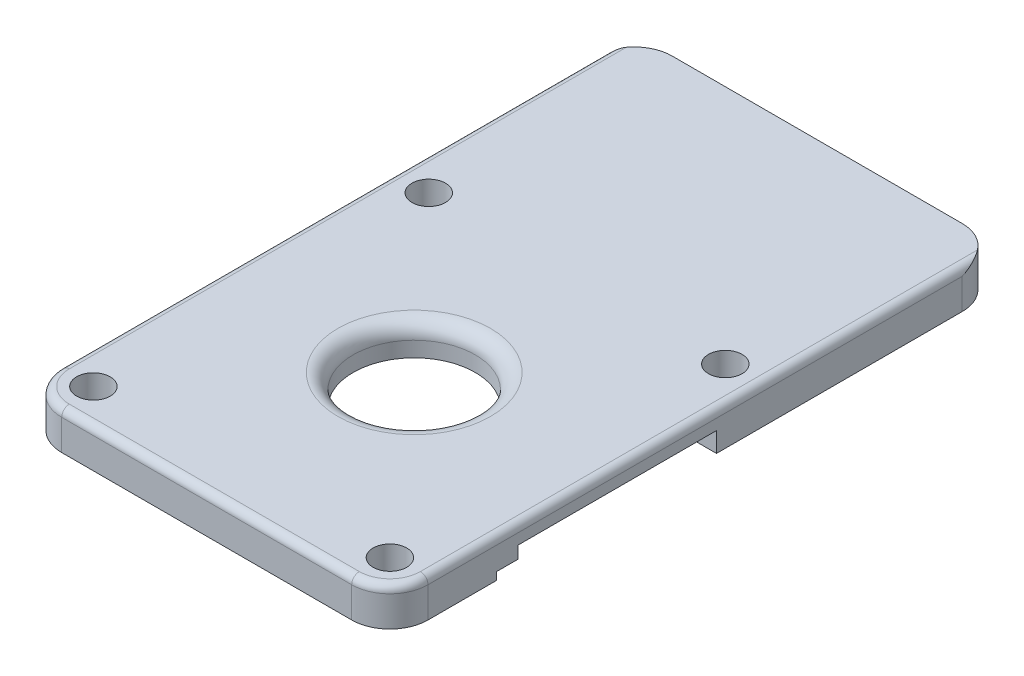
SolidWorks part; units mm, degrees
ref_plane "前视基准面" through (0, 0, 0) normal (0, 0, 1) x (1, 0, 0)
ref_plane "上视基准面" through (0, 0, 0) normal (0, 1, 0) x (1, 0, 0)
ref_plane "右视基准面" through (0, 0, 0) normal (1, 0, 0) x (0, 0, -1)
sketch "草图1" plane through (0, 0, 0) normal (0, 1, 0) x (1, 0, 0)
  line L0 (-12, 10.776) -> (-12, 24.224)
  line L18 (-9.5, 13.276) -> (9.5, 13.276) construction
  line L19 (-12, 10.776) -> (-12, -10.776)
  line L20 (-9.5, -13.276) -> (9.5, -13.276)
  line L21 (12, 10.776) -> (12, -10.776)
  line L22 (-12, 13.276) -> (12, -13.276) construction
  line L23 (-12, -13.276) -> (12, 13.276) construction
  line L24 (-9.5, 26.724) -> (9.5, 26.724)
  line L25 (12, 24.224) -> (12, 10.776)
  line L26 (-19.3805, 0) -> (19.2101, 0) construction
  line L27 (0, 33.0534) -> (0, -22.2948) construction
  line L37 (-9.715, 10.985) -> (9.715, -10.985) construction
  line L38 (-9.715, -10.985) -> (9.715, 10.985) construction
  line L39 (-9.714, 10.986) -> (9.714, 10.986) construction
  line L40 (-9.714, 10.986) -> (-9.714, -10.986) construction
  line L41 (-9.714, -10.986) -> (9.714, -10.986) construction
  line L42 (9.714, 10.986) -> (9.714, -10.986) construction
  line L43 (-9.714, 10.986) -> (9.714, -10.986) construction
  line L44 (-9.714, -10.986) -> (9.714, 10.986) construction
  arc A4 (-9.5, 13.276) -> (-12, 10.776) centre (-9.5, 10.776) ccw construction
  arc A5 (-9.5, -13.276) -> (-12, -10.776) centre (-9.5, -10.776) cw
  arc A6 (9.5, -13.276) -> (12, -10.776) centre (9.5, -10.776) ccw
  arc A7 (12, 10.776) -> (9.5, 13.276) centre (9.5, 10.776) ccw construction
  arc A8 (12, 24.224) -> (9.5, 26.724) centre (9.5, 24.224) ccw
  arc A9 (-12, 24.224) -> (-9.5, 26.724) centre (-9.5, 24.224) cw
  circle A12 centre (-9.714, -10.986) radius 2.2002
  circle A13 centre (-9.714, -10.986) radius 1.1
  circle A14 centre (9.714, -10.986) radius 1.1
  circle A15 centre (9.714, -10.986) radius 2.2002
  circle A16 centre (9.714, 10.986) radius 2.2002
  circle A17 centre (9.714, 10.986) radius 1.1
  circle A18 centre (-9.714, 10.986) radius 1.1
  circle A19 centre (-9.714, 10.986) radius 2.2002
  circle A20 centre (0, 0.32) radius 4
  point P0 (0, 0)
  point P28 (0, 0)
  point P34 (0, 0)
  dimension "D5" = 40
  dimension "D6" = 2.5
  dimension "D7" = 19.428
  dimension "D8" = 21.972
  dimension "D3" = 2.5
  dimension "D4" = 2.5
  dimension "D9" = 13.596
  dimension "D1" = 24
  dimension "D2" = 26.552
extrude "凸台-拉伸1" add sketch "草图1" against normal blind 2.5 contours A6 A15 L21 L25 A8 L24 A9 L0 L19 A5 A12 L20 A20 A16 A19 | A16 A17 | A19 A18 | A12 A13 | A15 A14
sketch "草图2" plane through (12, 0, 0) normal (1, 0, 0) x (0, 0, -1)
  line L0 (24.224, -2.5) -> (-10.776, -2.5) construction
  line L1 (-6.276, -2.5) -> (8.124, -2.5)
  line L2 (-6.276, -2.5) -> (-6.276, -2)
  line L3 (-6.276, -2) -> (8.124, -2)
  line L4 (8.124, -2.5) -> (8.124, -2)
  line L5 (-13.276, -2.5) -> (-13.276, 0) construction
  point P8 (8.124, -2.25)
  dimension "D1" = 21.4
  dimension "D2" = 7
  dimension "D3" = 0.5
extrude "切除-拉伸1" cut sketch "草图2" against normal through all
sketch "草图3" plane through (12, 0, 0) normal (1, 0, 0) x (0, 0, -1)
  line L0 (-13.276, -2.5) -> (-13.276, 0) construction
  line L1 (8.124, -2.5) -> (-4.876, -2.5)
  line L2 (8.124, -2.5) -> (8.124, -1.2)
  line L3 (8.124, -1.2) -> (-4.876, -1.2)
  line L4 (-4.876, -2.5) -> (-4.876, -1.2)
  dimension "D1" = 1.3
  dimension "D2" = 8.4
  dimension "D3" = 21.4
extrude "切除-拉伸2" cut sketch "草图3" against normal blind 4.5
sketch "草图4" plane through (-12, 0, 0) normal (-1, 0, 0) x (0, 0, 1)
  line L4 (-8.124, -2.5) -> (4.876, -2.5)
  line L5 (4.876, -2.5) -> (4.876, -1.2)
  line L6 (4.876, -1.2) -> (-8.124, -1.2)
  line L7 (-8.124, -1.2) -> (-8.124, -2.5)
  line L24 (-8.124, -2.5) -> (4.876, -2.5)
  line L25 (4.876, -2.5) -> (4.876, -1.2)
  line L26 (4.876, -1.2) -> (-8.124, -1.2)
  line L27 (-8.124, -1.2) -> (-8.124, -2.5)
  dimension "D2" = 0
extrude "切除-拉伸3" cut sketch "草图4" against normal blind 4.5 contours L24 L25 L26 L27
sketch "草图5" plane through (0, -2.5, 0) normal (0, -1, 0) x (1, 0, 0)
  line L0 (-12, -8.124) -> (12, -8.124) construction
  line L1 (-4, -8.124) -> (7.5, -8.124)
  line L2 (-4, -8.124) -> (-4, -25.424)
  line L3 (-4, -25.424) -> (7.5, -25.424)
  line L4 (7.5, -8.124) -> (7.5, -25.424)
  line L6 (7.5, -8.124) -> (7.5, 4.876) construction
  line L7 (12, -24.224) -> (12, -8.124) construction
  line L8 (-9.5, -26.724) -> (9.5, -26.724) construction
  dimension "D1" = 16
  dimension "D2" = 1.3
extrude "切除-拉伸11" cut sketch "草图5" against normal up to surface (0.5 mm away) contours L2 L1 L4 L3 up to face at (0, -2, 1.976)
sketch "草图6" plane through (0, -2, 0) normal (0, -1, 0) x (1, 0, 0)
  line L0 (-4, -8.124) -> (-4, -25.424) construction
  line L5 (-4, -8.124) -> (2, -8.124)
  line L6 (-4, -8.124) -> (-4, -18.124)
  line L7 (-4, -18.124) -> (2, -18.124)
  line L8 (2, -8.124) -> (2, -18.124)
  line L9 (-7.5, -8.124) -> (-4, -8.124) construction
  line L10 (12, -24.224) -> (12, -8.124) construction
  line L11 (-12, -8.124) -> (-4, -8.124) construction
  dimension "D1" = 10
  dimension "D2" = 10
extrude "切除-拉伸12" cut sketch "草图6" against normal blind 0.5
fillet "圆角1" radius 0.5 5 edges at (-11.2678, 0, 12.5438) (0, 0, 13.276) (11.2678, 0, 12.5438) (12, 0, -6.724) (-12, 0, -6.724)
fillet "圆角2" radius 1 1 edges at (0, 0, 3.68)
